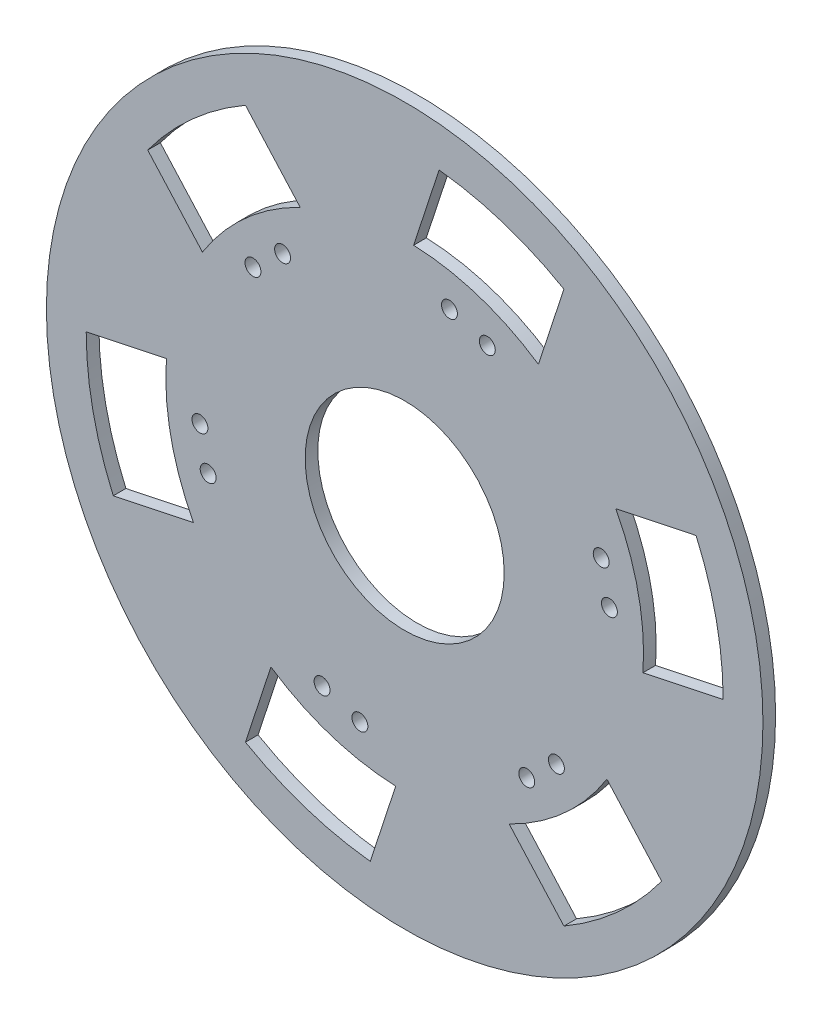
SolidWorks part; units mm, degrees
ref_plane "Front Plane" through (0, 0, 0) normal (0, 0, 1) x (1, 0, 0)
ref_plane "Top Plane" through (0, 0, 0) normal (0, 1, 0) x (1, 0, 0)
ref_plane "Right Plane" through (0, 0, 0) normal (1, 0, 0) x (0, 0, -1)
sketch "Sketch1" plane through (0, 0, 0) normal (0, 0, 1) x (1, 0, 0)
  circle A0 centre (0, 0) radius 90
  circle A1 centre (0, 0) radius 25
  dimension "D1" = 180
  dimension "D2" = 50
extrude "Boss-Extrude1" add sketch "Sketch1" along normal blind 3.175 contours A0 A1 region at (-87.4544, 0, 0)
sketch "Sketch2" plane through (0, 0, 0) normal (0, 0, -1) x (-1, 0, 0)
  circle A0 centre (-49.3631, 15.5091) radius 2
  circle A1 centre (-51.4246, 5.7238) radius 2
  circle A2 centre (-38.1128, -34.9952) radius 2
  circle A3 centre (-30.6693, -41.6731) radius 2
  circle A4 centre (11.2503, -50.5043) radius 2
  circle A5 centre (20.7553, -47.3969) radius 2
  circle A6 centre (49.3631, -15.5091) radius 2
  circle A7 centre (51.4246, -5.7238) radius 2
  circle A8 centre (38.1128, 34.9952) radius 2
  circle A9 centre (30.6693, 41.6731) radius 2
  circle A10 centre (-20.7553, 47.3969) radius 2
  circle A11 centre (-11.2503, 50.5043) radius 2
extrude "Cut-Extrude1" cut sketch "Sketch2" against normal through all
sketch "Sketch3" plane through (0, 0, 3.175) normal (0, 0, 1) x (1, 0, 0)
  line L0 (-49.3631, -15.5091) -> (-51.4246, -5.7238) construction
  line L1 (-20.7553, -47.3969) -> (-11.2503, -50.5043) construction
  line L2 (30.6693, -41.6731) -> (38.1128, -34.9952) construction
  line L3 (49.3631, 15.5091) -> (51.4246, 5.7238) construction
  line L4 (20.7553, 47.3969) -> (11.2503, 50.5043) construction
  line L5 (-30.6693, 41.6731) -> (-38.1128, 34.9952) construction
  line L6 (-88.0669, -18.553) -> (88.0669, 18.553) construction
  line L7 (-27.9661, -85.5447) -> (27.9661, 85.5447) construction
  line L8 (60.1009, -66.9917) -> (-60.1009, 66.9917) construction
  line L9 (-80, 0) -> (-62.1109, 3.7687)
  line L10 (-80, 0) -> (-73.2007, -32.2747)
  line L11 (-62.1109, 3.7687) -> (-55.3116, -28.506)
  line L12 (-73.2007, -32.2747) -> (-55.3116, -28.506)
  line L13 (-64.2562, -30.3904) -> (-71.0555, 1.8843) construction
  line L14 (-73.2007, -32.2747) -> (-53.0503, -28.0296)
  line L15 (-80, 0) -> (-59.8496, 4.2451)
  line L16 (-40, 69.282) -> (-27.7917, 55.674)
  line L17 (-40, 69.282) -> (-64.5511, 47.2563)
  line L18 (-64.5511, 47.2563) -> (-52.3428, 33.6483)
  line L19 (-27.7917, 55.674) -> (-52.3428, 33.6483)
  line L20 (-40, 69.282) -> (-26.2485, 53.9538)
  line L21 (-64.5511, 47.2563) -> (-50.7996, 31.9281)
  line L22 (40, 69.282) -> (34.3192, 51.9053)
  line L23 (40, 69.282) -> (8.6496, 79.531)
  line L24 (8.6496, 79.531) -> (2.9689, 62.1543)
  line L25 (34.3192, 51.9053) -> (2.9689, 62.1543)
  line L26 (40, 69.282) -> (33.6012, 49.7088)
  line L27 (8.6496, 79.531) -> (2.2508, 59.9578)
  line L28 (80, 0) -> (62.1109, -3.7687)
  line L29 (80, 0) -> (73.2007, 32.2747)
  line L30 (73.2007, 32.2747) -> (55.3116, 28.506)
  line L31 (62.1109, -3.7687) -> (55.3116, 28.506)
  line L32 (80, 0) -> (59.8496, -4.2451)
  line L33 (73.2007, 32.2747) -> (53.0503, 28.0296)
  line L34 (40, -69.282) -> (27.7917, -55.674)
  line L35 (40, -69.282) -> (64.5511, -47.2563)
  line L36 (64.5511, -47.2563) -> (52.3428, -33.6483)
  line L37 (27.7917, -55.674) -> (52.3428, -33.6483)
  line L38 (40, -69.282) -> (26.2485, -53.9538)
  line L39 (64.5511, -47.2563) -> (50.7996, -31.9281)
  line L40 (-40, -69.282) -> (-34.3192, -51.9053)
  line L41 (-40, -69.282) -> (-8.6496, -79.531)
  line L42 (-8.6496, -79.531) -> (-2.9689, -62.1543)
  line L43 (-34.3192, -51.9053) -> (-2.9689, -62.1543)
  line L44 (-40, -69.282) -> (-33.6012, -49.7088)
  line L45 (-8.6496, -79.531) -> (-2.2508, -59.9578)
  circle A0 centre (0, 0) radius 60
  circle A1 centre (0, 0) radius 80
  circle A2 centre (0, 0) radius 90 construction
  point P19 (0, 0)
  point P38 (0, 0)
  point P45 (0, 0)
  point P46 (-67.6558, -14.253)
  point P81 (0, 0)
  dimension "D1" = 120
  dimension "D2" = 160
  dimension "D3" = 6
extrude "Cut-Extrude2" cut sketch "Sketch3" against normal through all contours L10 L12 L11 L9 | L10 A1 | A0 L15 L11 | A0 L11 L14 | L43 L40 L41 L42 | A0 L44 L43 | A0 L43 L45 | L41 A1 | L37 L34 L35 L36 | A0 L38 L37 | A0 L37 L39 | L35 A1 | L31 L28 L29 L30 | A0 L31 L33 | A0 L32 L31 | L29 A1 | L19 L16 L17 L18 | L25 L22 L23 L24 | A0 L25 L27 | A0 L26 L25 | L23 A1 | L17 A1 | A0 L19 L21 | A0 L20 L19 region at (-67.6558, -14.253, 3.175) region at (-77.2735, -16.2792, 3.175) region at (-60.5882, -0.1075, 3.175) region at (-52.7349, 58.7812, 3.175) region at (-46.1714, 51.4652, 3.175) region at (-55.4822, -24.345, 3.175) region at (-21.4844, -65.7182, 3.175) region at (-24.5386, -75.0604, 3.175) region at (-48.8244, 35.8765, 3.175) region at (-30.201, -52.5247, 3.175) region at (-30.3872, 52.4172, 3.175) region at (24.5386, 75.0604, 3.175) region at (21.4844, 65.7182, 3.175) region at (-6.6577, -60.2214, 3.175) region at (46.1714, -51.4652, 3.175) region at (52.7349, -58.7812, 3.175) region at (6.6577, 60.2214, 3.175) region at (30.3872, -52.4172, 3.175) region at (30.201, 52.5247, 3.175) region at (77.2735, 16.2792, 3.175) region at (67.6558, 14.253, 3.175) region at (48.8244, -35.8765, 3.175) region at (55.4822, 24.345, 3.175) region at (60.5882, 0.1075, 3.175)
